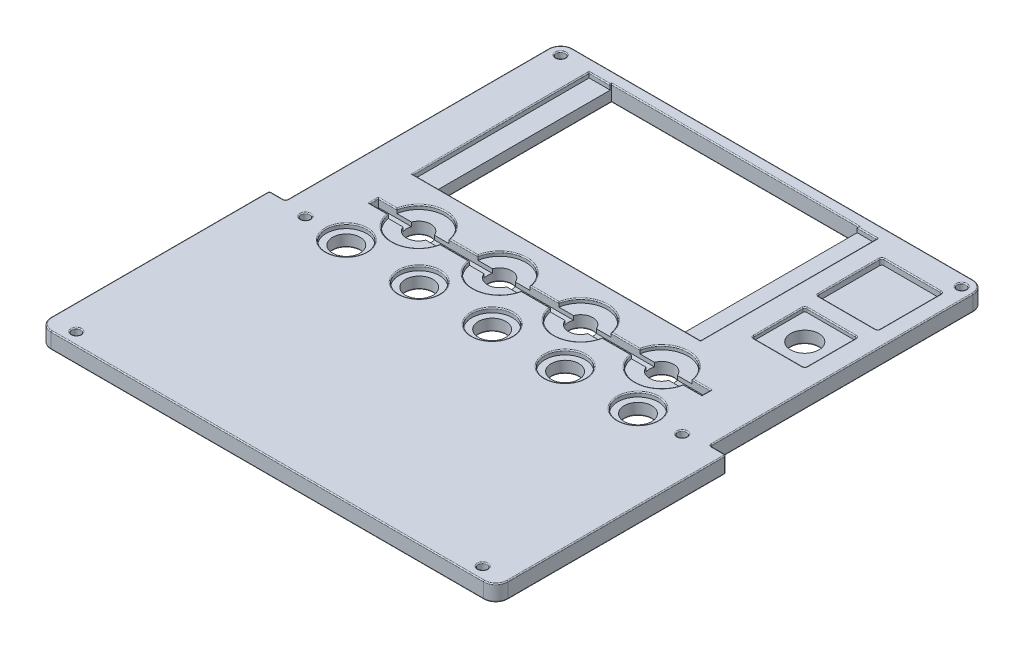
SolidWorks part; units mm, degrees
ref_plane "Front Plane" through (0, 0, 0) normal (0, 0, 1) x (1, 0, 0)
ref_plane "Top Plane" through (0, 0, 0) normal (0, 1, 0) x (1, 0, 0)
ref_plane "Right Plane" through (0, 0, 0) normal (1, 0, 0) x (0, 0, -1)
sketch "Sketch1" plane through (0, 0, 0) normal (0, 1, 0) x (1, 0, 0)
  line L0 (112.8, 56.9) -> (108.8, 56.9)
  line L1 (0, 0) -> (112.8, 0)
  line L2 (0, 0) -> (0, 56.9)
  line L3 (0, 56.9) -> (112.8, 56.9) construction
  line L4 (112.8, 0) -> (112.8, 56.9)
  line L5 (4, 56.9) -> (0, 56.9)
  line L6 (4, 56.9) -> (4, 124.8)
  line L7 (4, 124.8) -> (108.8, 124.8)
  line L8 (108.8, 56.9) -> (108.8, 124.8)
  line L9 (0, 56.9) -> (112.8, 56.9) construction
  dimension "D1" = 104.8
  dimension "D2" = 112.8
  dimension "D3" = 67.9
  dimension "D4" = 56.9
extrude "Main" add sketch "Sketch1" along normal blind 4
sketch "Outline Display" plane through (0, 0, 0) normal (0, -1, 0) x (1, 0, 0)
  line L0 (4, -124.8) -> (4, -81.05) construction
  line L1 (4, -124.8) -> (4, -56.9) construction
  line L2 (4, -81.05) -> (17, -81.05) construction
  line L3 (17, -81.05) -> (17, -78.32) construction
  line L4 (14.23, -78.32) -> (85.03, -78.32) construction
  line L5 (14.23, -78.32) -> (14.23, -121.62) construction
  line L6 (14.23, -121.62) -> (85.03, -121.62) construction
  line L7 (85.03, -78.32) -> (85.03, -121.62) construction
  line L8 (17, -81.05) -> (14.23, -81.05) construction
  point P7 (17, -81.05)
  dimension "D1" = 43.75
  dimension "D2" = 13
  dimension "D3" = 2.73
  dimension "D4" = 2.77
  dimension "D5" = 43.3
  dimension "D6" = 70.8
sketch "Display PCB Notch" plane through (0, 4, 0) normal (0, -1, 0) x (1, 0, 0)
  line L0 (14.23, -78.32) -> (14.23, -78.22) construction
  line L1 (14.13, -78.22) -> (85.13, -78.22)
  line L2 (14.13, -78.22) -> (14.13, -121.72)
  line L3 (14.13, -121.72) -> (85.13, -121.72)
  line L4 (85.13, -78.22) -> (85.13, -121.72)
  line L5 (14.23, -78.32) -> (14.13, -78.32) construction
  line L6 (85.03, -121.62) -> (85.03, -121.72) construction
  line L7 (85.03, -121.62) -> (85.13, -121.62) construction
  dimension "D2" = 0.1
extrude "PCB Notch" cut sketch "Display PCB Notch" along normal blind 1.2
sketch "Sketch4" plane through (0, 0, 0) normal (0, -1, 0) x (-1, 0, 0)
  line L0 (-14.23, 78.32) -> (-85.03, 78.32) construction
  line L1 (-19.33, 78.87) -> (-80.29, 78.87)
  line L2 (-19.33, 78.87) -> (-19.33, 122.05)
  line L3 (-19.33, 122.05) -> (-80.29, 122.05)
  line L4 (-80.29, 78.87) -> (-80.29, 122.05)
  dimension "D1" = 5.1
  dimension "D2" = 0.55
  dimension "D3" = 60.96
  dimension "D4" = 43.18
extrude "Display Cut" cut sketch "Sketch4" against normal up to next
sketch "Sketch5" plane through (0, 0, 0) normal (0, -1, 0) x (1, 0, 0)
  line L0 (108.8, -56.9) -> (108.8, -124.8) construction
  line L1 (89.12, -102.2) -> (97.32, -102.2) construction
  line L2 (97.32, -102.2) -> (97.32, -91.75) construction
  circle A0 centre (97.32, -91.75) radius 3.5
  point P0 (89.12, -102.2)
  point P1 (108.8, -124.8)
  point P9 (97.32, -91.75)
  dimension "D5" = 7
  dimension "D1" = 22.6
  dimension "D2" = 19.68
  dimension "D3" = 10.45
  dimension "D4" = 8.2
extrude "Rotary Hole" cut sketch "Sketch5" against normal up to next
sketch "Sketch6" plane through (0, 0, 0) normal (0, -1, 0) x (1, 0, 0)
  line L0 (6.9, -124.8) -> (6.9, -121.9) construction
  line L1 (108.8, -124.8) -> (4, -124.8) construction
  line L2 (6.9, -121.9) -> (4, -121.9) construction
  line L3 (4, -124.8) -> (4, -56.9) construction
  line L4 (56.4, 0) -> (56.4, -124.8) construction
  line L5 (0, 0) -> (112.8, 0) construction
  line L6 (0, -55.9) -> (9.9, -55.9) construction
  line L7 (0, -56.9) -> (0, 0) construction
  line L8 (4, -56.9) -> (0, -56.9) construction
  line L9 (0, -3) -> (6.25, -3) construction
  circle A0 centre (6.9, -121.9) radius 1.1
  circle A1 centre (9.9, -55.9) radius 1.1
  circle A2 centre (6.25, -3) radius 1.1
  circle A3 centre (105.9, -121.9) radius 1.1
  circle A4 centre (102.9, -55.9) radius 1.1
  circle A5 centre (106.55, -3) radius 1.1
  dimension "D1" = 2.2
  dimension "D7" = 6.25
  dimension "D2" = 2.9
  dimension "D3" = 2.9
  dimension "D4" = 9.9
  dimension "D5" = 1
  dimension "D6" = 3
extrude "Mounts" cut sketch "Sketch6" against normal up to next contours A0 | A1 | A2 | A5 | A4 | A3
fillet "Fillet1" radius 3 4 edges at (112.8, 2, 0) (108.8, 2, -124.8) (4, 2, -124.8) (0, 2, 0)
sketch "Sketch7" plane through (0, 0, 0) normal (0, -1, 0) x (1, 0, 0)
  line L0 (17, -81.05) -> (17, -75.8) construction
  line L1 (17, -59.7) -> (4, -59.7) construction
  line L2 (17, -75.8) -> (95.8, -75.8)
  line L3 (17, -75.8) -> (17, -59.7)
  line L4 (17, -59.7) -> (95.8, -59.7)
  line L5 (95.8, -75.8) -> (95.8, -59.7)
  line L6 (4, -121.8) -> (4, -56.9) construction
  line L7 (95.8, -59.7) -> (108.8, -59.7) construction
  line L8 (108.8, -56.9) -> (108.8, -121.8) construction
  line L9 (17, -67.75) -> (95.8, -67.75) construction
  circle A0 centre (26, -67.75) radius 3
  circle A1 centre (46, -67.75) radius 3
  circle A2 centre (66, -67.75) radius 3
  circle A3 centre (86, -67.75) radius 3
  dimension "D3" = 6
  dimension "D1" = 5.25
  dimension "D2" = 16.1
  dimension "D4" = 9
  dimension "D5" = 20
  dimension "D6" = 20
  dimension "D7" = 20
extrude "Toggle Mounts" cut sketch "Sketch7" against normal up to next contours A0 | A1 | A2 | A3 region at (26, 0, -67.75) region at (46, 0, -67.75) region at (66, 0, -67.75) region at (86, 0, -67.75)
sketch "Sketch8" plane through (0, 4, 0) normal (0, -1, 0) x (1, 0, 0)
  line L0 (89, -67.75) -> (23, -67.75) construction
  line L1 (97, -67.75) -> (89, -67.75) construction
  line L2 (97, -68.8) -> (15, -68.8)
  line L3 (97, -68.8) -> (97, -66.7)
  line L4 (97, -66.7) -> (15, -66.7)
  line L5 (15, -68.8) -> (15, -66.7)
  line L6 (23, -67.75) -> (15, -67.75) construction
  line L7 (23, -67.75) -> (23, -68.8) construction
  line L8 (23, -67.75) -> (23, -66.7) construction
  circle A0 centre (86, -67.75) radius 3 construction
  circle A1 centre (26, -67.75) radius 3 construction
  circle A2 centre (86, -67.75) radius 3 construction
  circle A3 centre (86, -67.75) radius 3 construction
  circle A4 centre (26, -67.75) radius 3 construction
  circle A5 centre (26, -67.75) radius 3 construction
  dimension "D1" = 8
  dimension "D2" = 2.1
extrude "Toggle Direction" cut sketch "Sketch8" along normal blind 2
sketch "Sketch9" plane through (0, 4, 0) normal (0, 1, 0) x (1, 0, 0)
  circle A0 centre (26, 67.75) radius 6.5
  circle A1 centre (46, 67.75) radius 6.5
  circle A2 centre (66, 67.75) radius 6.5
  circle A3 centre (86, 67.75) radius 6.5
  point P0 (26, 67.75)
  point P1 (46, 67.75)
  point P3 (66, 67.75)
  point P5 (86, 67.75)
  dimension "D1" = 13
extrude "Toggle Countersinks" cut sketch "Sketch9" against normal blind 1
sketch "Sketch10" plane through (0, 4, 0) normal (0, 1, 0) x (1, 0, 0)
  line L1 (90.82, 98.25) -> (103.82, 98.25)
  line L2 (90.82, 98.25) -> (90.82, 85.25)
  line L3 (90.82, 85.25) -> (103.82, 85.25)
  line L4 (103.82, 98.25) -> (103.82, 85.25)
  line L5 (90.82, 98.25) -> (103.82, 85.25) construction
  line L6 (90.82, 85.25) -> (103.82, 98.25) construction
  point P0 (97.32, 91.75)
  point P1 (97.32, 91.75)
  dimension "D1" = 13
extrude "Encoder Clearance" cut sketch "Sketch10" against normal blind 1
sketch "Sketch11" plane through (0, 4, 0) normal (0, 1, 0) x (1, 0, 0)
  line L1 (89.82, 102.25) -> (104.82, 102.25)
  line L2 (89.82, 102.25) -> (89.82, 118.25)
  line L3 (89.82, 118.25) -> (104.82, 118.25)
  line L4 (104.82, 102.25) -> (104.82, 118.25)
  line L5 (89.82, 102.25) -> (104.82, 118.25) construction
  line L6 (89.82, 118.25) -> (104.82, 102.25) construction
  line L10 (103.82, 85.25) -> (103.82, 98.25)
  line L11 (103.82, 98.25) -> (90.82, 98.25)
  line L12 (90.82, 98.25) -> (90.82, 85.25)
  line L13 (90.82, 85.25) -> (103.82, 85.25)
  line L14 (103.82, 85.25) -> (103.82, 98.25) construction
  line L15 (103.82, 98.25) -> (90.82, 98.25) construction
  line L16 (90.82, 98.25) -> (90.82, 85.25) construction
  line L17 (90.82, 85.25) -> (103.82, 85.25) construction
  point P4 (97.32, 110.25)
  dimension "D2" = 1
  dimension "D3" = 1
  dimension "D4" = 4
  dimension "D5" = 16
  dimension "D1" = 0
extrude "Encoder Pin Clearance" cut sketch "Sketch11" against normal blind 1.5
fillet "Fillet2" radius 0.5 12 edges at (0, 2, -56.9) (4, 2, -56.9) (112.8, 2, -56.9) (108.8, 2, -56.9) (89.82, 3.25, -102.25) (89.82, 3.25, -118.25) (104.82, 3.25, -118.25) (104.82, 3.25, -102.25) (103.82, 3.5, -85.25) (103.82, 3.5, -98.25) (90.82, 3.5, -98.25) (90.82, 3.5, -85.25)
sketch "Sketch12" plane through (0, 4, 0) normal (0, 1, 0) x (1, 0, 0)
  line L0 (9.9, 55.9) -> (102.9, 55.9) construction
  line L1 (38, 66.7) -> (38, 59.3) construction
  line L3 (56, 66.7) -> (56, 59.3) construction
  line L4 (59.5854, 66.7) -> (52.4146, 66.7) construction
  line L5 (74, 66.7) -> (74, 59.3) construction
  line L7 (38, 59.3) -> (20, 59.3) construction
  line L8 (38, 59.3) -> (56, 59.3) construction
  line L9 (74, 59.3) -> (92, 59.3) construction
  line L10 (56, 59.3) -> (74, 59.3) construction
  circle A2 centre (20, 55.9) radius 3.4
  circle A3 centre (38, 55.9) radius 3.4
  circle A4 centre (56, 55.9) radius 3.4
  circle A5 centre (74, 55.9) radius 3.4
  circle A6 centre (92, 55.9) radius 3.4
  point P3 (9.9, 55.9)
  point P4 (102.9, 55.9)
  dimension "D1" = 6.8
  dimension "D2" = 18
extrude "LED Mounts" cut sketch "Sketch12" against normal up to next
sketch "Sketch13" plane through (0, 4, 0) normal (0, 1, 0) x (1, 0, 0)
  circle A0 centre (20, 55.9) radius 5
  circle A1 centre (38, 55.9) radius 5
  circle A2 centre (56, 55.9) radius 5
  circle A3 centre (74, 55.9) radius 5
  circle A4 centre (92, 55.9) radius 5
  point P0 (20, 55.9)
  point P1 (38, 55.9)
  point P3 (56, 55.9)
  point P5 (74, 55.9)
  point P7 (92, 55.9)
  dimension "D1" = 10
extrude "LED Countersink" cut sketch "Sketch13" against normal blind 1.1
fillet "Fillet4" radius 0.25 107 edges at (4, 4, -89.6) (4.8787, 4, -123.9213) (56.4, 4, -124.8) (111.9213, 4, -0.8787) (56.4, 4, 0) (4, 0, -89.6) (4.8787, 0, -123.9213) (56.4, 0, -124.8) (112.8, 0, -29.7) (111.9213, 0, -0.8787) (56.4, 0, 0) (108.9464, 4, -57.0464) (108.9464, 0, -57.0464) (3.8536, 4, -57.0464) (3.8536, 0, -57.0464) (90.9664, 4, -85.3964) (90.9664, 4, -98.1036) (103.6736, 4, -98.1036) (103.6736, 4, -85.3964) (104.6736, 4, -102.3964) (104.6736, 4, -118.1036) (89.9664, 4, -118.1036) (89.9664, 4, -102.3964) (0.1464, 4, -56.7536) (112.6536, 4, -56.7536) (0.1464, 0, -56.7536) (112.6536, 0, -56.7536) (107.9213, 4, -123.9213) (0.8787, 4, -0.8787) (107.9213, 0, -123.9213) (0.8787, 0, -0.8787) (2, 4, -56.9) (108.8, 4, -89.6) (110.8, 4, -56.9) (112.8, 4, -29.7) (0, 4, -29.7) (2, 0, -56.9) (108.8, 0, -89.6) (110.8, 0, -56.9) (0, 0, -29.7) (49.63, 4, -78.22) (85.13, 4, -99.97) (82.71, 4, -121.72) (16.73, 4, -121.72) (14.13, 4, -99.97) (49.81, 0, -78.87) (80.29, 0, -100.46) (49.81, 0, -122.05) (19.33, 0, -100.46) (97.32, 0, -95.25) (9.9, 4, -54.8) (9.9, 0, -57) (6.25, 4, -1.9) (6.25, 0, -4.1) (106.55, 0, -1.9) (106.55, 4, -1.9) (102.9, 0, -54.8) (102.9, 4, -54.8) (105.9, 0, -120.8) (105.9, 4, -120.8) (26, 0, -70.75) (46, 0, -70.75) (66, 0, -70.75) (86, 0, -70.75) (17.2927, 4, -68.8) (36, 4, -68.8) (56, 4, -68.8) (76, 4, -68.8) (94.7073, 4, -68.8) (15, 4, -67.75) (94.7073, 4, -66.7) (76, 4, -66.7) (56, 4, -66.7) (36, 4, -66.7) (17.2927, 4, -66.7) (97, 4, -67.75) (26, 4, -74.25) (26, 4, -61.25) (46, 4, -74.25) (46, 4, -61.25) (66, 4, -74.25) (66, 4, -61.25) (86, 4, -74.25) (86, 4, -61.25) (97.32, 4, -85.25) (90.82, 4, -91.75) (97.32, 4, -98.25) (103.82, 4, -91.75) (97.32, 4, -118.25) (104.82, 4, -110.25) (97.32, 4, -102.25) (89.82, 4, -110.25) (92, 0, -52.5) (20, 0, -52.5) (38, 0, -52.5) (56, 0, -52.5) (74, 0, -52.5) (20, 4, -50.9) (38, 4, -50.9) (56, 4, -50.9) (74, 4, -50.9) (92, 4, -50.9) (6.9, 4, -120.8) (80.29, 4, -121.885) (49.81, 4, -122.05) (19.33, 4, -121.885) (6.9, 0, -123)
